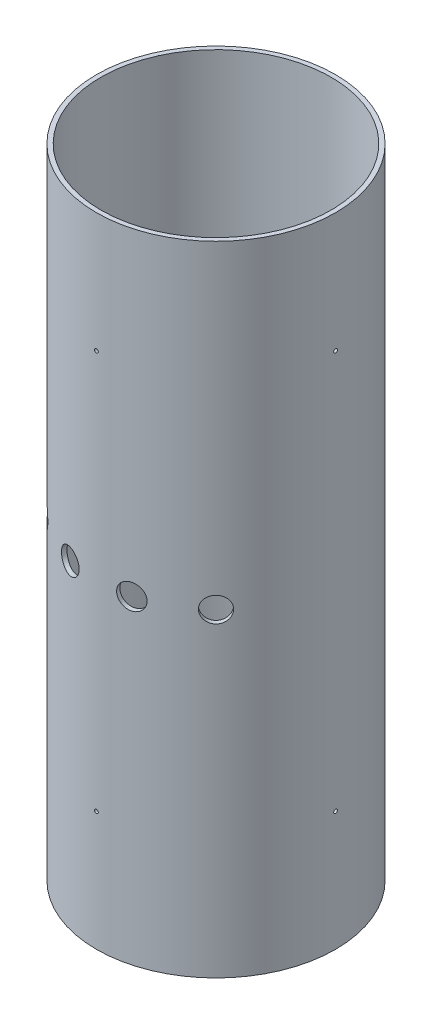
SolidWorks part; units mm, degrees
material "E-Glass Fiber"
ref_plane "Front Plane" through (0, 0, 0) normal (0, 0, 1) x (1, 0, 0)
ref_plane "Top Plane" through (0, 0, 0) normal (0, 1, 0) x (1, 0, 0)
ref_plane "Right Plane" through (0, 0, 0) normal (1, 0, 0) x (0, 0, -1)
sketch "Coupler Profile" plane through (0, 0, 0) normal (0, 1, 0) x (1, 0, 0)
  circle A0 centre (0, 0) radius 73.3425
  circle A1 centre (0, 0) radius 76.1746
  dimension "D1" = 146.685
  dimension "D2" = 152.3492
extrude "Coupler Body" add sketch "Coupler Profile" along normal blind 406.4
sketch "Sketch1" plane through (0, 0, 0) normal (0, 0, 1) x (1, 0, 0)
  line L0 (76.1746, 406.4) -> (-76.1746, 406.4) construction
  circle A0 centre (0, 76.2) radius 1.1906
  circle A1 centre (0, 330.2) radius 1.1906
  dimension "D3" = 2.3813
  dimension "D1" = 76.2
  dimension "D2" = 76.2
extrude "Cut-Extrude1" cut sketch "Sketch1" against normal through all both and the other way through all
pattern_circular "CirPattern1" count 4 over 360 about axis through (0, 0, 0) along (0, 1, 0) of "Cut-Extrude1"
sketch "Center Axis" plane through (0, 0, 0) normal (0, 0, 1) x (1, 0, 0)
  line L0 (0, 0) -> (0, 406.4) construction
  line L1 (73.3425, 406.4) -> (-73.3425, 406.4) construction
ref_plane "Offset Plane" through (0, 0, 0) normal (0.7071, 0, 0.7071) x (0, 1, 0)
sketch "Sketch3" plane through (0, 0, 0) normal (0.7071, 0, 0.7071) x (0, 1, 0)
  line L0 (0, 0) -> (406.4, 0) construction
  circle A0 centre (203.2, 0) radius 7.9375
  dimension "D1" = 15.875
extrude "Key Hole Cuts" cut sketch "Sketch3" along normal through all
pattern_circular "Key Hole Pattern" count 4 over 90 about axis through (0, 406.4, 0) along (0, 1, 0) of "Key Hole Cuts" reverse direction yes
sketch "Sketch4" plane through (0, 0, 0) normal (0, 0, 1) x (1, 0, 0)
  line L0 (-76.1746, 203.2) -> (76.1746, 203.2) construction
  line L1 (-76.1746, 329.0094) -> (-76.1746, 77.3906) construction
  line L2 (76.1746, 77.3906) -> (76.1746, 329.0094) construction
  circle A0 centre (0, 203.2) radius 3.175
  dimension "D1" = 6.35
extrude "Cut-Extrude2" cut sketch "Sketch4" against normal through all
equation "\"Length\"=16"
equation "\"Outer Diameter\"= 5.998"
equation "\"Inner Diameter\"= 5.775"
equation "\"Wall Thickness\"= 0.111"
equation "\"D1@Coupler Profile\" = \"Inner Diameter\""
equation "\"D2@Coupler Profile\" = \"Outer Diameter\""
equation "\"D1@Coupler Body\" = \"Length\""
equation "\"Shear Pin Dia\"= 3 / 32"
equation "\"Shear Pin Offset\"= 3"
equation "\"D1@Sketch1\"=\"Shear Pin Offset\""
equation "\"D2@Sketch1\"=\"Shear Pin Offset\""
equation "\"D3@Sketch1\"=\"Shear Pin Dia\""
equation "\"Key Hole Dia\"= 0.625"
equation "\"D1@Sketch3\"=\"Key Hole Dia\""
